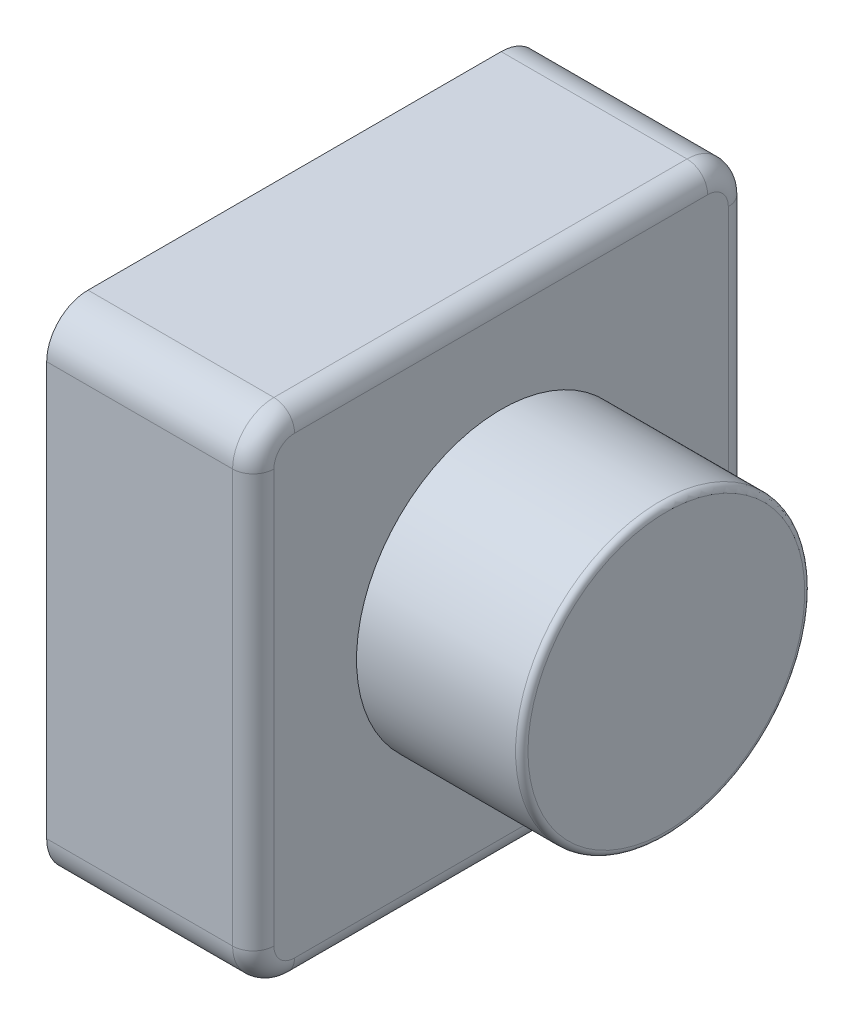
SolidWorks part; units mm, degrees
material "Plain Carbon Steel"
ref_plane "Front Plane" through (0, 0, 0) normal (0, 0, 1) x (1, 0, 0)
ref_plane "Top Plane" through (0, 0, 0) normal (0, 1, 0) x (1, 0, 0)
ref_plane "Right Plane" through (0, 0, 0) normal (1, 0, 0) x (0, 0, -1)
sketch "Sketch1" plane through (0, 0, 0) normal (1, 0, 0) x (0, 0, -1)
  line L1 (0, 0) -> (-120, 0)
  line L2 (0, 0) -> (0, 120)
  line L3 (0, 120) -> (-120, 120)
  line L4 (-120, 0) -> (-120, 120)
  dimension "D1" = 120
  dimension "D2" = 120
extrude "Boss-Extrude1" add sketch "Sketch1" along normal blind 50
sketch "Sketch2" plane through (50, 0, 0) normal (1, 0, 0) x (0, 0, -1)
  line L0 (0, 120) -> (-120, 120) construction
  line L1 (0, 0) -> (0, 120) construction
  circle A0 centre (-60, 60) radius 35
  dimension "D1" = 70
  dimension "D2" = 60
  dimension "D3" = 60
extrude "Boss-Extrude2" add sketch "Sketch2" along normal blind 40
sketch "Sketch3" plane through (90, 0, 0) normal (1, 0, 0) x (0, 0, -1)
  circle A0 centre (-60, 60) radius 25
  dimension "D1" = 50
extrude "Cut-Extrude1" cut sketch "Sketch3" against normal through all both and the other way through all
fillet "Fillet2" radius 10 4 edges at (25, 0, 0) (25, 0, 120) (25, 120, 120) (25, 120, 0)
fillet "Fillet3" radius 1.5 1 edges at (90, 60, 25)
fillet "Fillet5" radius 5 9 edges at (50, 2.9289, 117.0711) (50, 60, 120) (50, 117.0711, 117.0711) (50, 120, 60) (50, 117.0711, 2.9289) (50, 60, 0) (50, 2.9289, 2.9289) (50, 0, 60) (50, 60, 35)
shell "Shell1" thickness 2 removed face at (0, 60, 35)
